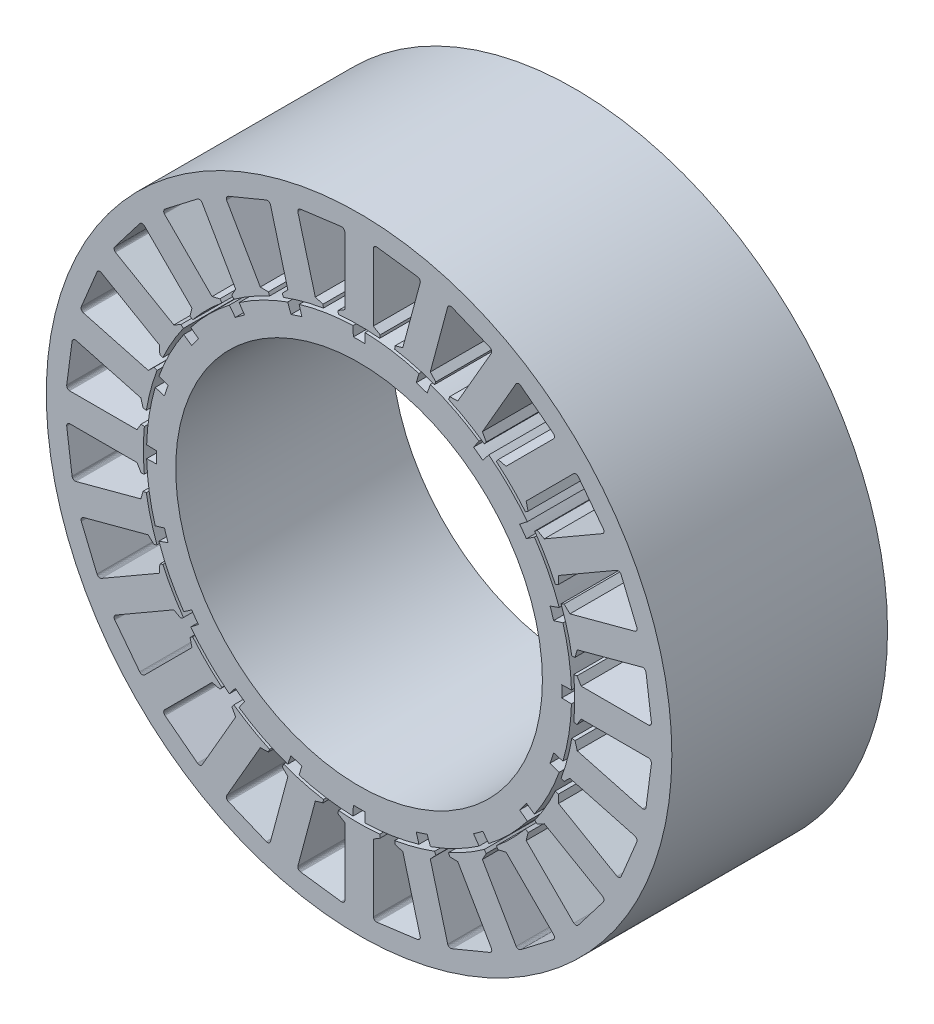
SolidWorks part; units mm, degrees
ref_plane "Ön Düzlem" through (0, 0, 0) normal (0, 0, 1) x (1, 0, 0)
ref_plane "Üst Düzlem" through (0, 0, 0) normal (0, 1, 0) x (1, 0, 0)
ref_plane "Sağ Düzlem" through (0, 0, 0) normal (1, 0, 0) x (0, 0, -1)
sketch "Model" plane through (0, 0, 0) normal (0, 0, 1) x (1, 0, 0)
  line L1 (60.5945, 121.4987) -> (60.8885, 121.3363)
  line L2 (60.8885, 121.3363) -> (61.139, 121.1124)
  line L3 (61.139, 121.1124) -> (61.3334, 120.8385)
  line L4 (61.3334, 120.8385) -> (61.4619, 120.5282)
  line L5 (61.4619, 120.5282) -> (61.5182, 120.197)
  line L6 (61.5182, 120.197) -> (61.4993, 119.8617)
  line L7 (61.4993, 119.8617) -> (61.4063, 119.5389)
  line L8 (61.4063, 119.5389) -> (45.7726, 92.4605)
  line L9 (45.7726, 92.4605) -> (42.0525, 92.3778)
  line L10 (42.0525, 92.3778) -> (41.4785, 90.992)
  line L11 (58.0621, 81.4174) -> (58.9753, 82.6074)
  line L12 (58.9753, 82.6074) -> (57.1868, 85.8705)
  line L13 (57.1868, 85.8705) -> (72.8206, 112.9489)
  line L14 (72.8206, 112.9489) -> (73.0536, 113.1908)
  line L15 (73.0536, 113.1908) -> (73.3346, 113.3748)
  line L16 (73.3346, 113.3748) -> (73.6495, 113.4917)
  line L17 (73.6495, 113.4917) -> (73.9825, 113.5355)
  line L18 (73.9825, 113.5355) -> (74.317, 113.5041)
  line L19 (74.317, 113.5041) -> (74.636, 113.3991)
  line L20 (74.636, 113.3991) -> (74.9237, 113.2258)
  line L21 (74.9237, 113.2258) -> (89.976, 101.6758)
  line L22 (89.976, 101.6758) -> (90.2179, 101.4427)
  line L23 (90.2179, 101.4427) -> (90.4019, 101.1617)
  line L24 (90.4019, 101.1617) -> (90.5188, 100.8468)
  line L25 (90.5188, 100.8468) -> (90.5626, 100.5138)
  line L26 (90.5626, 100.5138) -> (90.5313, 100.1793)
  line L27 (90.5313, 100.1793) -> (90.4263, 99.8603)
  line L28 (90.4263, 99.8603) -> (90.2529, 99.5726)
  line L29 (90.2529, 99.5726) -> (68.1435, 77.4631)
  line L30 (68.1435, 77.4631) -> (64.5287, 78.3461)
  line L31 (64.5287, 78.3461) -> (63.6156, 77.1561)
  line L32 (77.1561, 63.6156) -> (78.3461, 64.5287)
  line L33 (78.3461, 64.5287) -> (77.4631, 68.1435)
  line L34 (77.4631, 68.1435) -> (99.5726, 90.2529)
  line L35 (99.5726, 90.2529) -> (99.8603, 90.4263)
  line L36 (99.8603, 90.4263) -> (100.1793, 90.5313)
  line L37 (100.1793, 90.5313) -> (100.5138, 90.5626)
  line L38 (100.5138, 90.5626) -> (100.8468, 90.5188)
  line L39 (100.8468, 90.5188) -> (101.1617, 90.4019)
  line L40 (101.1617, 90.4019) -> (101.4427, 90.2179)
  line L41 (101.4427, 90.2179) -> (101.6758, 89.976)
  line L42 (101.6758, 89.976) -> (113.2258, 74.9237)
  line L43 (113.2258, 74.9237) -> (113.3991, 74.636)
  line L44 (113.3991, 74.636) -> (113.5041, 74.317)
  line L45 (113.5041, 74.317) -> (113.5355, 73.9825)
  line L46 (113.5355, 73.9825) -> (113.4917, 73.6495)
  line L47 (113.4917, 73.6495) -> (113.3748, 73.3346)
  line L48 (113.3748, 73.3346) -> (113.1908, 73.0536)
  line L49 (113.1908, 73.0536) -> (112.9489, 72.8206)
  line L50 (112.9489, 72.8206) -> (85.8705, 57.1868)
  line L51 (85.8705, 57.1868) -> (82.6074, 58.9753)
  line L52 (82.6074, 58.9753) -> (81.4174, 58.0621)
  line L53 (90.992, 41.4785) -> (92.3778, 42.0525)
  line L54 (92.3778, 42.0525) -> (92.4605, 45.7726)
  line L55 (92.4605, 45.7726) -> (119.5389, 61.4063)
  line L56 (119.5389, 61.4063) -> (119.8617, 61.4993)
  line L57 (119.8617, 61.4993) -> (120.197, 61.5182)
  line L58 (120.197, 61.5182) -> (120.5282, 61.4619)
  line L59 (120.5282, 61.4619) -> (120.8385, 61.3334)
  line L60 (120.8385, 61.3334) -> (121.1124, 61.139)
  line L61 (121.1124, 61.139) -> (121.3363, 60.8885)
  line L62 (121.3363, 60.8885) -> (121.4987, 60.5945)
  line L63 (121.4987, 60.5945) -> (128.7594, 43.0658)
  line L64 (128.7594, 43.0658) -> (128.8524, 42.743)
  line L65 (128.8524, 42.743) -> (128.8712, 42.4076)
  line L66 (128.8712, 42.4076) -> (128.815, 42.0765)
  line L67 (128.815, 42.0765) -> (128.6864, 41.7662)
  line L68 (128.6864, 41.7662) -> (128.492, 41.4922)
  line L69 (128.492, 41.4922) -> (128.2416, 41.2684)
  line L70 (128.2416, 41.2684) -> (127.9476, 41.1059)
  line L71 (127.9476, 41.1059) -> (97.7455, 33.0133)
  line L72 (97.7455, 33.0133) -> (95.0566, 35.5853)
  line L73 (95.0566, 35.5853) -> (93.6707, 35.0113)
  line L74 (98.6269, 16.5147) -> (100.1141, 16.7105)
  line L75 (100.1141, 16.7105) -> (101.1568, 20.2824)
  line L76 (101.1568, 20.2824) -> (131.3588, 28.375)
  line L77 (131.3588, 28.375) -> (131.6947, 28.3813)
  line L78 (131.6947, 28.3813) -> (132.0235, 28.3127)
  line L79 (132.0235, 28.3127) -> (132.3288, 28.1726)
  line L80 (132.3288, 28.1726) -> (132.5953, 27.9682)
  line L81 (132.5953, 27.9682) -> (132.8096, 27.7095)
  line L82 (132.8096, 27.7095) -> (132.9609, 27.4097)
  line L83 (132.9609, 27.4097) -> (133.0418, 27.0836)
  line L84 (133.0418, 27.0836) -> (135.5183, 8.273)
  line L85 (135.5183, 8.273) -> (135.5246, 7.9371)
  line L86 (135.5246, 7.9371) -> (135.4559, 7.6083)
  line L87 (135.4559, 7.6083) -> (135.3159, 7.303)
  line L88 (135.3159, 7.303) -> (135.1114, 7.0365)
  line L89 (135.1114, 7.0365) -> (134.8528, 6.8222)
  line L90 (134.8528, 6.8222) -> (134.5529, 6.6709)
  line L91 (134.5529, 6.6709) -> (134.2269, 6.59)
  line L92 (134.2269, 6.59) -> (102.9594, 6.59)
  line L93 (102.9594, 6.59) -> (101.0278, 9.7704)
  line L94 (101.0278, 9.7704) -> (99.5406, 9.5746)
  line L95 (99.5406, -9.5746) -> (101.0278, -9.7704)
  line L96 (101.0278, -9.7704) -> (102.9594, -6.59)
  line L97 (102.9594, -6.59) -> (134.2269, -6.59)
  line L98 (134.2269, -6.59) -> (134.5529, -6.6709)
  line L99 (134.5529, -6.6709) -> (134.8528, -6.8222)
  line L100 (134.8528, -6.8222) -> (135.1114, -7.0365)
  line L101 (135.1114, -7.0365) -> (135.3159, -7.303)
  line L102 (135.3159, -7.303) -> (135.4559, -7.6083)
  line L103 (135.4559, -7.6083) -> (135.5246, -7.9371)
  line L104 (135.5246, -7.9371) -> (135.5183, -8.273)
  line L105 (135.5183, -8.273) -> (133.0418, -27.0836)
  line L106 (133.0418, -27.0836) -> (132.9609, -27.4097)
  line L107 (132.9609, -27.4097) -> (132.8096, -27.7095)
  line L108 (132.8096, -27.7095) -> (132.5953, -27.9682)
  line L109 (132.5953, -27.9682) -> (132.3288, -28.1726)
  line L110 (132.3288, -28.1726) -> (132.0235, -28.3127)
  line L111 (132.0235, -28.3127) -> (131.6947, -28.3813)
  line L112 (131.6947, -28.3813) -> (131.3588, -28.375)
  line L113 (131.3588, -28.375) -> (101.1568, -20.2824)
  line L114 (101.1568, -20.2824) -> (100.1141, -16.7105)
  line L115 (100.1141, -16.7105) -> (98.6269, -16.5147)
  line L116 (93.6707, -35.0113) -> (95.0566, -35.5853)
  line L117 (95.0566, -35.5853) -> (97.7455, -33.0133)
  line L118 (97.7455, -33.0133) -> (127.9476, -41.1059)
  line L119 (127.9476, -41.1059) -> (128.2416, -41.2684)
  line L120 (128.2416, -41.2684) -> (128.492, -41.4922)
  line L121 (128.492, -41.4922) -> (128.6864, -41.7662)
  line L122 (128.6864, -41.7662) -> (128.815, -42.0765)
  line L123 (128.815, -42.0765) -> (128.8712, -42.4076)
  line L124 (128.8712, -42.4076) -> (128.8524, -42.743)
  line L125 (128.8524, -42.743) -> (128.7594, -43.0658)
  line L126 (128.7594, -43.0658) -> (121.4987, -60.5945)
  line L127 (121.4987, -60.5945) -> (121.3363, -60.8885)
  line L128 (121.3363, -60.8885) -> (121.1124, -61.139)
  line L129 (121.1124, -61.139) -> (120.8385, -61.3334)
  line L130 (120.8385, -61.3334) -> (120.5282, -61.4619)
  line L131 (120.5282, -61.4619) -> (120.197, -61.5182)
  line L132 (120.197, -61.5182) -> (119.8617, -61.4993)
  line L133 (119.8617, -61.4993) -> (119.5389, -61.4063)
  line L134 (119.5389, -61.4063) -> (92.4605, -45.7726)
  line L135 (92.4605, -45.7726) -> (92.3778, -42.0525)
  line L136 (92.3778, -42.0525) -> (90.992, -41.4785)
  line L137 (81.4174, -58.0621) -> (82.6074, -58.9753)
  line L138 (82.6074, -58.9753) -> (85.8705, -57.1868)
  line L139 (85.8705, -57.1868) -> (112.9489, -72.8206)
  line L140 (112.9489, -72.8206) -> (113.1908, -73.0536)
  line L141 (113.1908, -73.0536) -> (113.3748, -73.3346)
  line L142 (113.3748, -73.3346) -> (113.4917, -73.6495)
  line L143 (113.4917, -73.6495) -> (113.5355, -73.9825)
  line L144 (113.5355, -73.9825) -> (113.5041, -74.317)
  line L145 (113.5041, -74.317) -> (113.3991, -74.636)
  line L146 (113.3991, -74.636) -> (113.2258, -74.9237)
  line L147 (113.2258, -74.9237) -> (101.6758, -89.976)
  line L148 (101.6758, -89.976) -> (101.4427, -90.2179)
  line L149 (101.4427, -90.2179) -> (101.1617, -90.4019)
  line L150 (101.1617, -90.4019) -> (100.8468, -90.5188)
  line L151 (100.8468, -90.5188) -> (100.5138, -90.5626)
  line L152 (100.5138, -90.5626) -> (100.1793, -90.5313)
  line L153 (100.1793, -90.5313) -> (99.8603, -90.4263)
  line L154 (99.8603, -90.4263) -> (99.5726, -90.2529)
  line L155 (99.5726, -90.2529) -> (77.4631, -68.1435)
  line L156 (77.4631, -68.1435) -> (78.3461, -64.5287)
  line L157 (78.3461, -64.5287) -> (77.1561, -63.6156)
  line L158 (63.6156, -77.1561) -> (64.5287, -78.3461)
  line L159 (64.5287, -78.3461) -> (68.1435, -77.4631)
  line L160 (68.1435, -77.4631) -> (90.2529, -99.5726)
  line L161 (90.2529, -99.5726) -> (90.4263, -99.8603)
  line L162 (90.4263, -99.8603) -> (90.5313, -100.1793)
  line L163 (90.5313, -100.1793) -> (90.5626, -100.5138)
  line L164 (90.5626, -100.5138) -> (90.5188, -100.8468)
  line L165 (90.5188, -100.8468) -> (90.4019, -101.1617)
  line L166 (90.4019, -101.1617) -> (90.2179, -101.4427)
  line L167 (90.2179, -101.4427) -> (89.976, -101.6758)
  line L168 (89.976, -101.6758) -> (74.9237, -113.2258)
  line L169 (74.9237, -113.2258) -> (74.636, -113.3991)
  line L170 (74.636, -113.3991) -> (74.317, -113.5041)
  line L171 (74.317, -113.5041) -> (73.9825, -113.5355)
  line L172 (73.9825, -113.5355) -> (73.6495, -113.4917)
  line L173 (73.6495, -113.4917) -> (73.3346, -113.3748)
  line L174 (73.3346, -113.3748) -> (73.0536, -113.1908)
  line L175 (73.0536, -113.1908) -> (72.8206, -112.9489)
  line L176 (72.8206, -112.9489) -> (57.1868, -85.8705)
  line L177 (57.1868, -85.8705) -> (58.9753, -82.6074)
  line L178 (58.9753, -82.6074) -> (58.0621, -81.4174)
  line L179 (41.4785, -90.992) -> (42.0525, -92.3778)
  line L180 (42.0525, -92.3778) -> (45.7726, -92.4605)
  line L181 (45.7726, -92.4605) -> (61.4063, -119.5389)
  line L182 (61.4063, -119.5389) -> (61.4993, -119.8617)
  line L183 (61.4993, -119.8617) -> (61.5182, -120.197)
  line L184 (61.5182, -120.197) -> (61.4619, -120.5282)
  line L185 (61.4619, -120.5282) -> (61.3334, -120.8385)
  line L186 (61.3334, -120.8385) -> (61.139, -121.1124)
  line L187 (61.139, -121.1124) -> (60.8885, -121.3363)
  line L188 (60.8885, -121.3363) -> (60.5945, -121.4987)
  line L189 (60.5945, -121.4987) -> (43.0658, -128.7594)
  line L190 (43.0658, -128.7594) -> (42.743, -128.8524)
  line L191 (42.743, -128.8524) -> (42.4076, -128.8712)
  line L192 (42.4076, -128.8712) -> (42.0765, -128.815)
  line L193 (42.0765, -128.815) -> (41.7662, -128.6864)
  line L194 (41.7662, -128.6864) -> (41.4922, -128.492)
  line L195 (41.4922, -128.492) -> (41.2684, -128.2416)
  line L196 (41.2684, -128.2416) -> (41.1059, -127.9476)
  line L197 (41.1059, -127.9476) -> (33.0133, -97.7455)
  line L198 (33.0133, -97.7455) -> (35.5853, -95.0566)
  line L199 (35.5853, -95.0566) -> (35.0113, -93.6707)
  line L200 (16.5147, -98.6269) -> (16.7105, -100.1141)
  line L201 (16.7105, -100.1141) -> (20.2824, -101.1568)
  line L202 (20.2824, -101.1568) -> (28.375, -131.3588)
  line L203 (28.375, -131.3588) -> (28.3813, -131.6947)
  line L204 (28.3813, -131.6947) -> (28.3127, -132.0235)
  line L205 (28.3127, -132.0235) -> (28.1726, -132.3288)
  line L206 (28.1726, -132.3288) -> (27.9682, -132.5953)
  line L207 (27.9682, -132.5953) -> (27.7095, -132.8096)
  line L208 (27.7095, -132.8096) -> (27.4097, -132.9609)
  line L209 (27.4097, -132.9609) -> (27.0836, -133.0418)
  line L210 (27.0836, -133.0418) -> (8.273, -135.5183)
  line L211 (8.273, -135.5183) -> (7.9371, -135.5246)
  line L212 (7.9371, -135.5246) -> (7.6083, -135.4559)
  line L213 (7.6083, -135.4559) -> (7.303, -135.3159)
  line L214 (7.303, -135.3159) -> (7.0365, -135.1114)
  line L215 (7.0365, -135.1114) -> (6.8222, -134.8528)
  line L216 (6.8222, -134.8528) -> (6.6709, -134.5529)
  line L217 (6.6709, -134.5529) -> (6.59, -134.2269)
  line L218 (6.59, -134.2269) -> (6.59, -102.9594)
  line L219 (6.59, -102.9594) -> (9.7704, -101.0278)
  line L220 (9.7704, -101.0278) -> (9.5746, -99.5406)
  line L221 (-9.5746, -99.5406) -> (-9.7704, -101.0278)
  line L222 (-9.7704, -101.0278) -> (-6.59, -102.9594)
  line L223 (-6.59, -102.9594) -> (-6.59, -134.2269)
  line L224 (-6.59, -134.2269) -> (-6.6709, -134.5529)
  line L225 (-6.6709, -134.5529) -> (-6.8222, -134.8528)
  line L226 (-6.8222, -134.8528) -> (-7.0365, -135.1114)
  line L227 (-7.0365, -135.1114) -> (-7.303, -135.3159)
  line L228 (-7.303, -135.3159) -> (-7.6083, -135.4559)
  line L229 (-7.6083, -135.4559) -> (-7.9371, -135.5246)
  line L230 (-7.9371, -135.5246) -> (-8.273, -135.5183)
  line L231 (-8.273, -135.5183) -> (-27.0836, -133.0418)
  line L232 (-27.0836, -133.0418) -> (-27.4097, -132.9609)
  line L233 (-27.4097, -132.9609) -> (-27.7095, -132.8096)
  line L234 (-27.7095, -132.8096) -> (-27.9682, -132.5953)
  line L235 (-27.9682, -132.5953) -> (-28.1726, -132.3288)
  line L236 (-28.1726, -132.3288) -> (-28.3127, -132.0235)
  line L237 (-28.3127, -132.0235) -> (-28.3813, -131.6947)
  line L238 (-28.3813, -131.6947) -> (-28.375, -131.3588)
  line L239 (-28.375, -131.3588) -> (-20.2824, -101.1568)
  line L240 (-20.2824, -101.1568) -> (-16.7105, -100.1141)
  line L241 (-16.7105, -100.1141) -> (-16.5147, -98.6269)
  line L242 (-35.0113, -93.6707) -> (-35.5853, -95.0566)
  line L243 (-35.5853, -95.0566) -> (-33.0133, -97.7455)
  line L244 (-33.0133, -97.7455) -> (-41.1059, -127.9476)
  line L245 (-41.1059, -127.9476) -> (-41.2684, -128.2416)
  line L246 (-41.2684, -128.2416) -> (-41.4922, -128.492)
  line L247 (-41.4922, -128.492) -> (-41.7662, -128.6864)
  line L248 (-41.7662, -128.6864) -> (-42.0765, -128.815)
  line L249 (-42.0765, -128.815) -> (-42.4076, -128.8712)
  line L250 (-42.4076, -128.8712) -> (-42.743, -128.8524)
  line L251 (-42.743, -128.8524) -> (-43.0658, -128.7594)
  line L252 (-43.0658, -128.7594) -> (-60.5945, -121.4987)
  line L253 (-60.5945, -121.4987) -> (-60.8885, -121.3363)
  line L254 (-60.8885, -121.3363) -> (-61.139, -121.1124)
  line L255 (-61.139, -121.1124) -> (-61.3334, -120.8385)
  line L256 (-61.3334, -120.8385) -> (-61.4619, -120.5282)
  line L257 (-61.4619, -120.5282) -> (-61.5182, -120.197)
  line L258 (-61.5182, -120.197) -> (-61.4993, -119.8617)
  line L259 (-61.4993, -119.8617) -> (-61.4063, -119.5389)
  line L260 (-61.4063, -119.5389) -> (-45.7726, -92.4605)
  line L261 (-45.7726, -92.4605) -> (-42.0525, -92.3778)
  line L262 (-42.0525, -92.3778) -> (-41.4785, -90.992)
  line L263 (-58.0621, -81.4174) -> (-58.9753, -82.6074)
  line L264 (-58.9753, -82.6074) -> (-57.1868, -85.8705)
  line L265 (-57.1868, -85.8705) -> (-72.8206, -112.9489)
  line L266 (-72.8206, -112.9489) -> (-73.0536, -113.1908)
  line L267 (-73.0536, -113.1908) -> (-73.3346, -113.3748)
  line L268 (-73.3346, -113.3748) -> (-73.6495, -113.4917)
  line L269 (-73.6495, -113.4917) -> (-73.9825, -113.5355)
  line L270 (-73.9825, -113.5355) -> (-74.317, -113.5041)
  line L271 (-74.317, -113.5041) -> (-74.636, -113.3991)
  line L272 (-74.636, -113.3991) -> (-74.9237, -113.2258)
  line L273 (-74.9237, -113.2258) -> (-89.976, -101.6758)
  line L274 (-89.976, -101.6758) -> (-90.2179, -101.4427)
  line L275 (-90.2179, -101.4427) -> (-90.4019, -101.1617)
  line L276 (-90.4019, -101.1617) -> (-90.5188, -100.8468)
  line L277 (-90.5188, -100.8468) -> (-90.5626, -100.5138)
  line L278 (-90.5626, -100.5138) -> (-90.5313, -100.1793)
  line L279 (-90.5313, -100.1793) -> (-90.4263, -99.8603)
  line L280 (-90.4263, -99.8603) -> (-90.2529, -99.5726)
  line L281 (-90.2529, -99.5726) -> (-68.1435, -77.4631)
  line L282 (-68.1435, -77.4631) -> (-64.5287, -78.3461)
  line L283 (-64.5287, -78.3461) -> (-63.6156, -77.1561)
  line L284 (-77.1561, -63.6156) -> (-78.3461, -64.5287)
  line L285 (-78.3461, -64.5287) -> (-77.4631, -68.1435)
  line L286 (-77.4631, -68.1435) -> (-99.5726, -90.2529)
  line L287 (-99.5726, -90.2529) -> (-99.8603, -90.4263)
  line L288 (-99.8603, -90.4263) -> (-100.1793, -90.5313)
  line L289 (-100.1793, -90.5313) -> (-100.5138, -90.5626)
  line L290 (-100.5138, -90.5626) -> (-100.8468, -90.5188)
  line L291 (-100.8468, -90.5188) -> (-101.1617, -90.4019)
  line L292 (-101.1617, -90.4019) -> (-101.4427, -90.2179)
  line L293 (-101.4427, -90.2179) -> (-101.6758, -89.976)
  line L294 (-101.6758, -89.976) -> (-113.2258, -74.9237)
  line L295 (-113.2258, -74.9237) -> (-113.3991, -74.636)
  line L296 (-113.3991, -74.636) -> (-113.5041, -74.317)
  line L297 (-113.5041, -74.317) -> (-113.5355, -73.9825)
  line L298 (-113.5355, -73.9825) -> (-113.4917, -73.6495)
  line L299 (-113.4917, -73.6495) -> (-113.3748, -73.3346)
  line L300 (-113.3748, -73.3346) -> (-113.1908, -73.0536)
  line L301 (-113.1908, -73.0536) -> (-112.9489, -72.8206)
  line L302 (-112.9489, -72.8206) -> (-85.8705, -57.1868)
  line L303 (-85.8705, -57.1868) -> (-82.6074, -58.9753)
  line L304 (-82.6074, -58.9753) -> (-81.4174, -58.0621)
  line L305 (-90.992, -41.4785) -> (-92.3778, -42.0525)
  line L306 (-92.3778, -42.0525) -> (-92.4605, -45.7726)
  line L307 (-92.4605, -45.7726) -> (-119.5389, -61.4063)
  line L308 (-119.5389, -61.4063) -> (-119.8617, -61.4993)
  line L309 (-119.8617, -61.4993) -> (-120.197, -61.5182)
  line L310 (-120.197, -61.5182) -> (-120.5282, -61.4619)
  line L311 (-120.5282, -61.4619) -> (-120.8385, -61.3334)
  line L312 (-120.8385, -61.3334) -> (-121.1124, -61.139)
  line L313 (-121.1124, -61.139) -> (-121.3363, -60.8885)
  line L314 (-121.3363, -60.8885) -> (-121.4987, -60.5945)
  line L315 (-121.4987, -60.5945) -> (-128.7594, -43.0658)
  line L316 (-128.7594, -43.0658) -> (-128.8524, -42.743)
  line L317 (-128.8524, -42.743) -> (-128.8712, -42.4076)
  line L318 (-128.8712, -42.4076) -> (-128.815, -42.0765)
  line L319 (-128.815, -42.0765) -> (-128.6864, -41.7662)
  line L320 (-128.6864, -41.7662) -> (-128.492, -41.4922)
  line L321 (-128.492, -41.4922) -> (-128.2416, -41.2684)
  line L322 (-128.2416, -41.2684) -> (-127.9476, -41.1059)
  line L323 (-127.9476, -41.1059) -> (-97.7455, -33.0133)
  line L324 (-97.7455, -33.0133) -> (-95.0566, -35.5853)
  line L325 (-95.0566, -35.5853) -> (-93.6707, -35.0113)
  line L326 (-98.6269, -16.5147) -> (-100.1141, -16.7105)
  line L327 (-100.1141, -16.7105) -> (-101.1568, -20.2824)
  line L328 (-101.1568, -20.2824) -> (-131.3588, -28.375)
  line L329 (-131.3588, -28.375) -> (-131.6947, -28.3813)
  line L330 (-131.6947, -28.3813) -> (-132.0235, -28.3127)
  line L331 (-132.0235, -28.3127) -> (-132.3288, -28.1726)
  line L332 (-132.3288, -28.1726) -> (-132.5953, -27.9682)
  line L333 (-132.5953, -27.9682) -> (-132.8096, -27.7095)
  line L334 (-132.8096, -27.7095) -> (-132.9609, -27.4097)
  line L335 (-132.9609, -27.4097) -> (-133.0418, -27.0836)
  line L336 (-133.0418, -27.0836) -> (-135.5183, -8.273)
  line L337 (-135.5183, -8.273) -> (-135.5246, -7.9371)
  line L338 (-135.5246, -7.9371) -> (-135.4559, -7.6083)
  line L339 (-135.4559, -7.6083) -> (-135.3159, -7.303)
  line L340 (-135.3159, -7.303) -> (-135.1114, -7.0365)
  line L341 (-135.1114, -7.0365) -> (-134.8528, -6.8222)
  line L342 (-134.8528, -6.8222) -> (-134.5529, -6.6709)
  line L343 (-134.5529, -6.6709) -> (-134.2269, -6.59)
  line L344 (-134.2269, -6.59) -> (-102.9594, -6.59)
  line L345 (-102.9594, -6.59) -> (-101.0278, -9.7704)
  line L346 (-101.0278, -9.7704) -> (-99.5406, -9.5746)
  line L347 (-99.5406, 9.5746) -> (-101.0278, 9.7704)
  line L348 (-101.0278, 9.7704) -> (-102.9594, 6.59)
  line L349 (-102.9594, 6.59) -> (-134.2269, 6.59)
  line L350 (-134.2269, 6.59) -> (-134.5529, 6.6709)
  line L351 (-134.5529, 6.6709) -> (-134.8528, 6.8222)
  line L352 (-134.8528, 6.8222) -> (-135.1114, 7.0365)
  line L353 (-135.1114, 7.0365) -> (-135.3159, 7.303)
  line L354 (-135.3159, 7.303) -> (-135.4559, 7.6083)
  line L355 (-135.4559, 7.6083) -> (-135.5246, 7.9371)
  line L356 (-135.5246, 7.9371) -> (-135.5183, 8.273)
  line L357 (-135.5183, 8.273) -> (-133.0418, 27.0836)
  line L358 (-133.0418, 27.0836) -> (-132.9609, 27.4097)
  line L359 (-132.9609, 27.4097) -> (-132.8096, 27.7095)
  line L360 (-132.8096, 27.7095) -> (-132.5953, 27.9682)
  line L361 (-132.5953, 27.9682) -> (-132.3288, 28.1726)
  line L362 (-132.3288, 28.1726) -> (-132.0235, 28.3127)
  line L363 (-132.0235, 28.3127) -> (-131.6947, 28.3813)
  line L364 (-131.6947, 28.3813) -> (-131.3588, 28.375)
  line L365 (-131.3588, 28.375) -> (-101.1568, 20.2824)
  line L366 (-101.1568, 20.2824) -> (-100.1141, 16.7105)
  line L367 (-100.1141, 16.7105) -> (-98.6269, 16.5147)
  line L368 (-93.6707, 35.0113) -> (-95.0566, 35.5853)
  line L369 (-95.0566, 35.5853) -> (-97.7455, 33.0133)
  line L370 (-97.7455, 33.0133) -> (-127.9476, 41.1059)
  line L371 (-127.9476, 41.1059) -> (-128.2416, 41.2684)
  line L372 (-128.2416, 41.2684) -> (-128.492, 41.4922)
  line L373 (-128.492, 41.4922) -> (-128.6864, 41.7662)
  line L374 (-128.6864, 41.7662) -> (-128.815, 42.0765)
  line L375 (-128.815, 42.0765) -> (-128.8712, 42.4076)
  line L376 (-128.8712, 42.4076) -> (-128.8524, 42.743)
  line L377 (-128.8524, 42.743) -> (-128.7594, 43.0658)
  line L378 (-128.7594, 43.0658) -> (-121.4987, 60.5945)
  line L379 (-121.4987, 60.5945) -> (-121.3363, 60.8885)
  line L380 (-121.3363, 60.8885) -> (-121.1124, 61.139)
  line L381 (-121.1124, 61.139) -> (-120.8385, 61.3334)
  line L382 (-120.8385, 61.3334) -> (-120.5282, 61.4619)
  line L383 (-120.5282, 61.4619) -> (-120.197, 61.5182)
  line L384 (-120.197, 61.5182) -> (-119.8617, 61.4993)
  line L385 (-119.8617, 61.4993) -> (-119.5389, 61.4063)
  line L386 (-119.5389, 61.4063) -> (-92.4605, 45.7726)
  line L387 (-92.4605, 45.7726) -> (-92.3778, 42.0525)
  line L388 (-92.3778, 42.0525) -> (-90.992, 41.4785)
  line L389 (-81.4174, 58.0621) -> (-82.6074, 58.9753)
  line L390 (-82.6074, 58.9753) -> (-85.8705, 57.1868)
  line L391 (-85.8705, 57.1868) -> (-112.9489, 72.8206)
  line L392 (-112.9489, 72.8206) -> (-113.1908, 73.0536)
  line L393 (-113.1908, 73.0536) -> (-113.3748, 73.3346)
  line L394 (-113.3748, 73.3346) -> (-113.4917, 73.6495)
  line L395 (-113.4917, 73.6495) -> (-113.5355, 73.9825)
  line L396 (-113.5355, 73.9825) -> (-113.5041, 74.317)
  line L397 (-113.5041, 74.317) -> (-113.3991, 74.636)
  line L398 (-113.3991, 74.636) -> (-113.2258, 74.9237)
  line L399 (-113.2258, 74.9237) -> (-101.6758, 89.976)
  line L400 (-101.6758, 89.976) -> (-101.4427, 90.2179)
  line L401 (-101.4427, 90.2179) -> (-101.1617, 90.4019)
  line L402 (-101.1617, 90.4019) -> (-100.8468, 90.5188)
  line L403 (-100.8468, 90.5188) -> (-100.5138, 90.5626)
  line L404 (-100.5138, 90.5626) -> (-100.1793, 90.5313)
  line L405 (-100.1793, 90.5313) -> (-99.8603, 90.4263)
  line L406 (-99.8603, 90.4263) -> (-99.5726, 90.2529)
  line L407 (-99.5726, 90.2529) -> (-77.4631, 68.1435)
  line L408 (-77.4631, 68.1435) -> (-78.3461, 64.5287)
  line L409 (-78.3461, 64.5287) -> (-77.1561, 63.6156)
  line L410 (-63.6156, 77.1561) -> (-64.5287, 78.3461)
  line L411 (-64.5287, 78.3461) -> (-68.1435, 77.4631)
  line L412 (-68.1435, 77.4631) -> (-90.2529, 99.5726)
  line L413 (-90.2529, 99.5726) -> (-90.4263, 99.8603)
  line L414 (-90.4263, 99.8603) -> (-90.5313, 100.1793)
  line L415 (-90.5313, 100.1793) -> (-90.5626, 100.5138)
  line L416 (-90.5626, 100.5138) -> (-90.5188, 100.8468)
  line L417 (-90.5188, 100.8468) -> (-90.4019, 101.1617)
  line L418 (-90.4019, 101.1617) -> (-90.2179, 101.4427)
  line L419 (-90.2179, 101.4427) -> (-89.976, 101.6758)
  line L420 (-89.976, 101.6758) -> (-74.9237, 113.2258)
  line L421 (-74.9237, 113.2258) -> (-74.636, 113.3991)
  line L422 (-74.636, 113.3991) -> (-74.317, 113.5041)
  line L423 (-74.317, 113.5041) -> (-73.9825, 113.5355)
  line L424 (-73.9825, 113.5355) -> (-73.6495, 113.4917)
  line L425 (-73.6495, 113.4917) -> (-73.3346, 113.3748)
  line L426 (-73.3346, 113.3748) -> (-73.0536, 113.1908)
  line L427 (-73.0536, 113.1908) -> (-72.8206, 112.9489)
  line L428 (-72.8206, 112.9489) -> (-57.1868, 85.8705)
  line L429 (-57.1868, 85.8705) -> (-58.9753, 82.6074)
  line L430 (-58.9753, 82.6074) -> (-58.0621, 81.4174)
  line L431 (-41.4785, 90.992) -> (-42.0525, 92.3778)
  line L432 (-42.0525, 92.3778) -> (-45.7726, 92.4605)
  line L433 (-45.7726, 92.4605) -> (-61.4063, 119.5389)
  line L434 (-61.4063, 119.5389) -> (-61.4993, 119.8617)
  line L435 (-61.4993, 119.8617) -> (-61.5182, 120.197)
  line L436 (-61.5182, 120.197) -> (-61.4619, 120.5282)
  line L437 (-61.4619, 120.5282) -> (-61.3334, 120.8385)
  line L438 (-61.3334, 120.8385) -> (-61.139, 121.1124)
  line L439 (-61.139, 121.1124) -> (-60.8885, 121.3363)
  line L440 (-60.8885, 121.3363) -> (-60.5945, 121.4987)
  line L441 (-60.5945, 121.4987) -> (-43.0658, 128.7594)
  line L442 (-43.0658, 128.7594) -> (-42.743, 128.8524)
  line L443 (-42.743, 128.8524) -> (-42.4076, 128.8712)
  line L444 (-42.4076, 128.8712) -> (-42.0765, 128.815)
  line L445 (-42.0765, 128.815) -> (-41.7662, 128.6864)
  line L446 (-41.7662, 128.6864) -> (-41.4922, 128.492)
  line L447 (-41.4922, 128.492) -> (-41.2684, 128.2416)
  line L448 (-41.2684, 128.2416) -> (-41.1059, 127.9476)
  line L449 (-41.1059, 127.9476) -> (-33.0133, 97.7455)
  line L450 (-33.0133, 97.7455) -> (-35.5853, 95.0566)
  line L451 (-35.5853, 95.0566) -> (-35.0113, 93.6707)
  line L452 (-16.5147, 98.6269) -> (-16.7105, 100.1141)
  line L453 (-16.7105, 100.1141) -> (-20.2824, 101.1568)
  line L454 (-20.2824, 101.1568) -> (-28.375, 131.3588)
  line L455 (-28.375, 131.3588) -> (-28.3813, 131.6947)
  line L456 (-28.3813, 131.6947) -> (-28.3127, 132.0235)
  line L457 (-28.3127, 132.0235) -> (-28.1726, 132.3288)
  line L458 (-28.1726, 132.3288) -> (-27.9682, 132.5953)
  line L459 (-27.9682, 132.5953) -> (-27.7095, 132.8096)
  line L460 (-27.7095, 132.8096) -> (-27.4097, 132.9609)
  line L461 (-27.4097, 132.9609) -> (-27.0836, 133.0418)
  line L462 (-27.0836, 133.0418) -> (-8.273, 135.5183)
  line L463 (-8.273, 135.5183) -> (-7.9371, 135.5246)
  line L464 (-7.9371, 135.5246) -> (-7.6083, 135.4559)
  line L465 (-7.6083, 135.4559) -> (-7.303, 135.3159)
  line L466 (-7.303, 135.3159) -> (-7.0365, 135.1114)
  line L467 (-7.0365, 135.1114) -> (-6.8222, 134.8528)
  line L468 (-6.8222, 134.8528) -> (-6.6709, 134.5529)
  line L469 (-6.6709, 134.5529) -> (-6.59, 134.2269)
  line L470 (-6.59, 134.2269) -> (-6.59, 102.9594)
  line L471 (-6.59, 102.9594) -> (-9.7704, 101.0278)
  line L472 (-9.7704, 101.0278) -> (-9.5746, 99.5406)
  line L473 (9.5746, 99.5406) -> (9.7704, 101.0278)
  line L474 (9.7704, 101.0278) -> (6.59, 102.9594)
  line L475 (6.59, 102.9594) -> (6.59, 134.2269)
  line L476 (6.59, 134.2269) -> (6.6709, 134.5529)
  line L477 (6.6709, 134.5529) -> (6.8222, 134.8528)
  line L478 (6.8222, 134.8528) -> (7.0365, 135.1114)
  line L479 (7.0365, 135.1114) -> (7.303, 135.3159)
  line L480 (7.303, 135.3159) -> (7.6083, 135.4559)
  line L481 (7.6083, 135.4559) -> (7.9371, 135.5246)
  line L482 (7.9371, 135.5246) -> (8.273, 135.5183)
  line L483 (8.273, 135.5183) -> (27.0836, 133.0418)
  line L484 (27.0836, 133.0418) -> (27.4097, 132.9609)
  line L485 (27.4097, 132.9609) -> (27.7095, 132.8096)
  line L486 (27.7095, 132.8096) -> (27.9682, 132.5953)
  line L487 (27.9682, 132.5953) -> (28.1726, 132.3288)
  line L488 (28.1726, 132.3288) -> (28.3127, 132.0235)
  line L489 (28.3127, 132.0235) -> (28.3813, 131.6947)
  line L490 (28.3813, 131.6947) -> (28.375, 131.3588)
  line L491 (28.375, 131.3588) -> (20.2824, 101.1568)
  line L492 (20.2824, 101.1568) -> (16.7105, 100.1141)
  line L493 (16.7105, 100.1141) -> (16.5147, 98.6269)
  line L494 (35.0113, 93.6707) -> (35.5853, 95.0566)
  line L495 (35.5853, 95.0566) -> (33.0133, 97.7455)
  line L496 (33.0133, 97.7455) -> (41.1059, 127.9476)
  line L497 (41.1059, 127.9476) -> (41.2684, 128.2416)
  line L498 (41.2684, 128.2416) -> (41.4922, 128.492)
  line L499 (41.4922, 128.492) -> (41.7662, 128.6864)
  line L500 (41.7662, 128.6864) -> (42.0765, 128.815)
  line L501 (42.0765, 128.815) -> (42.4076, 128.8712)
  line L502 (42.4076, 128.8712) -> (42.743, 128.8524)
  line L503 (42.743, 128.8524) -> (43.0658, 128.7594)
  line L504 (43.0658, 128.7594) -> (60.5945, 121.4987)
  line L506 (-94, 0) -> (-85, 0)
  line L507 (-85, 0) -> (-94, 0)
  line L508 (27.7776, -94.5021) -> (26.5086, -90.1848)
  line L509 (2.6574, -93.9624) -> (2.7847, -98.4606)
  line L510 (-27.7776, 94.5021) -> (-26.5086, 90.1848)
  line L511 (-2.6574, 93.9624) -> (-2.7847, 98.4606)
  line L512 (94.5021, 27.7776) -> (90.1848, 26.5086)
  line L513 (93.9624, 2.6574) -> (98.4606, 2.7847)
  line L514 (-94.5021, -27.7776) -> (-90.1848, -26.5086)
  line L515 (-93.9624, -2.6574) -> (-98.4606, -2.7847)
  line L516 (55.6209, -81.2931) -> (53.0798, -77.5792)
  line L517 (31.5634, -88.5424) -> (33.0744, -92.7811)
  line L518 (-55.6209, 81.2931) -> (-53.0798, 77.5792)
  line L519 (-31.5634, 88.5424) -> (-33.0744, 92.7811)
  line L520 (81.2931, 55.6209) -> (77.5792, 53.0798)
  line L521 (88.5424, 31.5634) -> (92.7811, 33.0744)
  line L522 (-81.2931, -55.6209) -> (-77.5792, -53.0798)
  line L523 (-88.5424, -31.5634) -> (-92.7811, -33.0744)
  line L524 (78.0195, -60.1265) -> (74.4552, -57.3796)
  line L525 (57.3796, -74.4552) -> (60.1265, -78.0195)
  line L526 (-78.0195, 60.1265) -> (-74.4552, 57.3796)
  line L527 (-57.3796, 74.4552) -> (-60.1265, 78.0195)
  line L528 (60.1265, 78.0195) -> (57.3796, 74.4552)
  line L529 (74.4552, 57.3796) -> (78.0195, 60.1265)
  line L530 (-60.1265, -78.0195) -> (-57.3796, -74.4552)
  line L531 (-74.4552, -57.3796) -> (-78.0195, -60.1265)
  line L532 (92.7811, -33.0744) -> (88.5424, -31.5634)
  line L533 (77.5792, -53.0798) -> (81.2931, -55.6209)
  line L534 (-92.7811, 33.0744) -> (-88.5424, 31.5634)
  line L535 (-77.5792, 53.0798) -> (-81.2931, 55.6209)
  line L536 (33.0744, 92.7811) -> (31.5634, 88.5424)
  line L537 (53.0798, 77.5792) -> (55.6209, 81.2931)
  line L538 (-33.0744, -92.7811) -> (-31.5634, -88.5424)
  line L539 (-53.0798, -77.5792) -> (-55.6209, -81.2931)
  line L540 (98.4606, -2.7847) -> (93.9624, -2.6574)
  line L541 (90.1848, -26.5086) -> (94.5021, -27.7776)
  line L542 (-98.4606, 2.7847) -> (-93.9624, 2.6574)
  line L543 (-90.1848, 26.5086) -> (-94.5021, 27.7776)
  line L544 (2.7847, 98.4606) -> (2.6574, 93.9624)
  line L545 (26.5086, 90.1848) -> (27.7776, 94.5021)
  line L546 (-2.7847, -98.4606) -> (-2.6574, -93.9624)
  line L547 (-26.5086, -90.1848) -> (-27.7776, -94.5021)
  arc A0 (145, 0) -> (64.7137, 129.758) centre (0, 0) ccw
  arc A1 (58.0621, 81.4174) -> (41.4785, 90.992) centre (0, 0) ccw
  arc A2 (77.1561, 63.6156) -> (63.6156, 77.1561) centre (0, 0) ccw
  arc A3 (90.992, 41.4785) -> (81.4174, 58.0621) centre (0, 0) ccw
  arc A4 (98.6269, 16.5147) -> (93.6707, 35.0113) centre (0, 0) ccw
  arc A5 (99.5406, -9.5746) -> (99.5406, 9.5746) centre (0, 0) ccw
  arc A6 (93.6707, -35.0113) -> (98.6269, -16.5147) centre (0, 0) ccw
  arc A7 (81.4174, -58.0621) -> (90.992, -41.4785) centre (0, 0) ccw
  arc A8 (63.6156, -77.1561) -> (77.1561, -63.6156) centre (0, 0) ccw
  arc A9 (41.4785, -90.992) -> (58.0621, -81.4174) centre (0, 0) ccw
  arc A10 (16.5147, -98.6269) -> (35.0113, -93.6707) centre (0, 0) ccw
  arc A11 (-9.5746, -99.5406) -> (9.5746, -99.5406) centre (0, 0) ccw
  arc A12 (-35.0113, -93.6707) -> (-16.5147, -98.6269) centre (0, 0) ccw
  arc A13 (-58.0621, -81.4174) -> (-41.4785, -90.992) centre (0, 0) ccw
  arc A14 (-77.1561, -63.6156) -> (-63.6156, -77.1561) centre (0, 0) ccw
  arc A15 (-90.992, -41.4785) -> (-81.4174, -58.0621) centre (0, 0) ccw
  arc A16 (-98.6269, -16.5147) -> (-93.6707, -35.0113) centre (0, 0) ccw
  arc A17 (-99.5406, 9.5746) -> (-99.5406, -9.5746) centre (0, 0) ccw
  arc A18 (-93.6707, 35.0113) -> (-98.6269, 16.5147) centre (0, 0) ccw
  arc A19 (-81.4174, 58.0621) -> (-90.992, 41.4785) centre (0, 0) ccw
  arc A20 (-63.6156, 77.1561) -> (-77.1561, 63.6156) centre (0, 0) ccw
  arc A21 (-41.4785, 90.992) -> (-58.0621, 81.4174) centre (0, 0) ccw
  arc A22 (-16.5147, 98.6269) -> (-35.0113, 93.6707) centre (0, 0) ccw
  arc A23 (9.5746, 99.5406) -> (-9.5746, 99.5406) centre (0, 0) ccw
  arc A24 (35.0113, 93.6707) -> (16.5147, 98.6269) centre (0, 0) ccw
  arc A25 (64.7137, 129.758) -> (145, 0) centre (0, 0) ccw
  arc A26 (94, 0) -> (-94, 0) centre (0, 0) ccw
  circle A27 centre (0, 0) radius 85
  arc A28 (-94, 0) -> (94, 0) centre (0, 0) ccw
  arc A29 (2.7847, -98.4606) -> (27.7776, -94.5021) centre (0, 0) ccw
  arc A30 (2.6574, -93.9624) -> (26.5086, -90.1848) centre (0, 0) ccw
  arc A31 (-2.7847, 98.4606) -> (-27.7776, 94.5021) centre (0, 0) ccw
  arc A32 (-2.6574, 93.9624) -> (-26.5086, 90.1848) centre (0, 0) ccw
  arc A33 (98.4606, 2.7847) -> (94.5021, 27.7776) centre (0, 0) ccw
  arc A34 (93.9624, 2.6574) -> (90.1848, 26.5086) centre (0, 0) ccw
  arc A35 (-98.4606, -2.7847) -> (-94.5021, -27.7776) centre (0, 0) ccw
  arc A36 (-93.9624, -2.6574) -> (-90.1848, -26.5086) centre (0, 0) ccw
  arc A37 (33.0744, -92.7811) -> (55.6209, -81.2931) centre (0, 0) ccw
  arc A38 (31.5634, -88.5424) -> (53.0798, -77.5792) centre (0, 0) ccw
  arc A39 (-33.0744, 92.7811) -> (-55.6209, 81.2931) centre (0, 0) ccw
  arc A40 (-31.5634, 88.5424) -> (-53.0798, 77.5792) centre (0, 0) ccw
  arc A41 (92.7811, 33.0744) -> (81.2931, 55.6209) centre (0, 0) ccw
  arc A42 (88.5424, 31.5634) -> (77.5792, 53.0798) centre (0, 0) ccw
  arc A43 (-92.7811, -33.0744) -> (-81.2931, -55.6209) centre (0, 0) ccw
  arc A44 (-88.5424, -31.5634) -> (-77.5792, -53.0798) centre (0, 0) ccw
  arc A45 (60.1265, -78.0195) -> (78.0195, -60.1265) centre (0, 0) ccw
  arc A46 (57.3796, -74.4552) -> (74.4552, -57.3796) centre (0, 0) ccw
  arc A47 (-60.1265, 78.0195) -> (-78.0195, 60.1265) centre (0, 0) ccw
  arc A48 (-57.3796, 74.4552) -> (-74.4552, 57.3796) centre (0, 0) ccw
  arc A49 (78.0195, 60.1265) -> (60.1265, 78.0195) centre (0, 0) ccw
  arc A50 (74.4552, 57.3796) -> (57.3796, 74.4552) centre (0, 0) ccw
  arc A51 (-78.0195, -60.1265) -> (-60.1265, -78.0195) centre (0, 0) ccw
  arc A52 (-74.4552, -57.3796) -> (-57.3796, -74.4552) centre (0, 0) ccw
  arc A53 (81.2931, -55.6209) -> (92.7811, -33.0744) centre (0, 0) ccw
  arc A54 (77.5792, -53.0798) -> (88.5424, -31.5634) centre (0, 0) ccw
  arc A55 (-81.2931, 55.6209) -> (-92.7811, 33.0744) centre (0, 0) ccw
  arc A56 (-77.5792, 53.0798) -> (-88.5424, 31.5634) centre (0, 0) ccw
  arc A57 (55.6209, 81.2931) -> (33.0744, 92.7811) centre (0, 0) ccw
  arc A58 (53.0798, 77.5792) -> (31.5634, 88.5424) centre (0, 0) ccw
  arc A59 (-55.6209, -81.2931) -> (-33.0744, -92.7811) centre (0, 0) ccw
  arc A60 (-53.0798, -77.5792) -> (-31.5634, -88.5424) centre (0, 0) ccw
  arc A61 (94.5021, -27.7776) -> (98.4606, -2.7847) centre (0, 0) ccw
  arc A62 (90.1848, -26.5086) -> (93.9624, -2.6574) centre (0, 0) ccw
  arc A63 (-94.5021, 27.7776) -> (-98.4606, 2.7847) centre (0, 0) ccw
  arc A64 (-90.1848, 26.5086) -> (-93.9624, 2.6574) centre (0, 0) ccw
  arc A65 (27.7776, 94.5021) -> (2.7847, 98.4606) centre (0, 0) ccw
  arc A66 (26.5086, 90.1848) -> (2.6574, 93.9624) centre (0, 0) ccw
  arc A67 (-27.7776, -94.5021) -> (-2.7847, -98.4606) centre (0, 0) ccw
  arc A68 (-26.5086, -90.1848) -> (-2.6574, -93.9624) centre (0, 0) ccw
extrude "Boss-Extrude1" add sketch "Model" along normal blind 100 contours A0 A25 A24 L494 L495 L496 L497 L498 L499 L500 L501 L502 L503 L504 L1 L2 L3 L4 L5 L6 L7 L8 L9 L10 A1 L11 L12 L13 L14 L15 L16 L17 L18 L19 L20 L21 L22 L23 L24 L25 L26 L27 L28 L29 L30 L31 A2 L32 L33 L34 | L511 A31 L510 A26 | L545 A65 L544 A26 | L521 A41 L520 A26 | L527 A47 L526 A26 | L535 A55 L534 A26 | L523 A43 L522 A28 | L531 A51 L530 A28 | L539 A59 L538 A28 | L517 A37 L516 A28 | L509 A29 L508 A28 | L525 A45 L524 A28 | L533 A53 L532 A28 | L541 A61 L540 A28 | L513 A33 L512 A26 | A39 L518 A40 L519 | A57 L536 A58 L537 | A49 L528 A50 L529 | A63 L542 A64 L543 | A35 L514 A36 L515 | A67 L546 A68 L547 | A28 A26 | A27 region at (-85.538, 43.5838, 0) region at (-85.538, -43.5838, 0) region at (-67.8834, 67.8834, 0) region at (-67.8834, -67.8834, 0) region at (-43.5838, -85.538, 0) region at (-15.018, 94.8196, 0) region at (15.018, 94.8196, 0) region at (15.018, -94.8196, 0) region at (43.5838, -85.538, 0) region at (67.8834, -67.8834, 0) region at (85.538, 43.5838, 0) region at (85.538, -43.5838, 0) region at (94.8196, 15.018, 0) region at (94.8196, -15.018, 0) region at (-119.8179, -74.136, 0)
